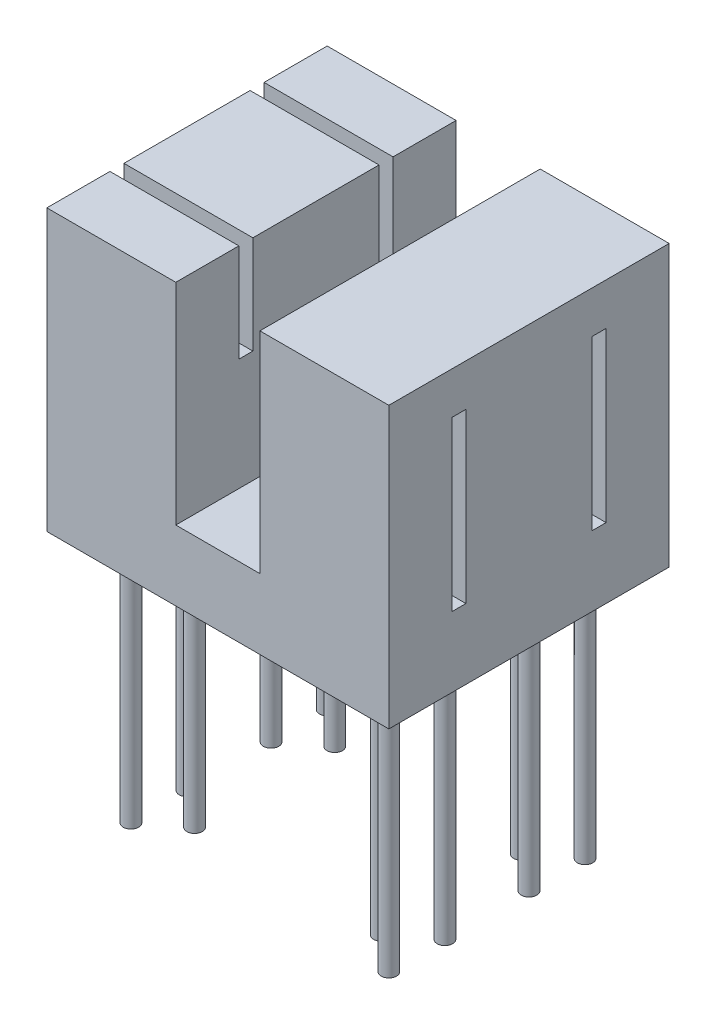
SolidWorks part; units mm, degrees
ref_plane "Front Plane" through (0, 0, 0) normal (0, 0, 1) x (1, 0, 0)
ref_plane "Top Plane" through (0, 0, 0) normal (0, 1, 0) x (1, 0, 0)
ref_plane "Right Plane" through (0, 0, 0) normal (1, 0, 0) x (0, 0, -1)
sketch "Sketch1" plane through (0, 0, 0) normal (0, 1, 0) x (1, 0, 0)
  line L0 (-1.5, 2.5) -> (-1.5, -2.5)
  line L1 (6.1, 2.5) -> (-6.1, 2.5)
  line L2 (6.1, 2.5) -> (6.1, -2.5)
  line L3 (6.1, -2.5) -> (-6.1, -2.5)
  line L4 (-6.1, 2.5) -> (-6.1, -2.5)
  line L5 (6.1, 2.5) -> (-6.1, -2.5) construction
  line L6 (6.1, -2.5) -> (-6.1, 2.5) construction
  line L7 (1.5, 2.5) -> (1.5, -2.5)
  line L8 (0, 4.5301) -> (0, -3.3555) construction
  point P0 (0, 0)
  dimension "D1" = 12.2
  dimension "D2" = 5
  dimension "D3" = 3
extrude "Boss-Extrude1" add sketch "Sketch1" along normal blind 7.5 contours L1 L4 L3 L0 | L1 L7 L3 L2 region at (-3.8, 0, 0) region at (3.8, 0, 0)
extrude "Boss-Extrude2" add sketch "Sketch1<4>" against normal blind 2.5 contours L1 L4 L3 L0 | L7 L1 L0 L3 | L1 L7 L3 L2 region at (0, 0, 0) region at (-3.8, 0, 0) region at (3.8, 0, 0)
sketch "Sketch1<4>" plane through (0, 0, 0) normal (0, 1, 0) x (1, 0, 0) same geometry as "Sketch1"
sketch "Sketch2" plane through (-1.5, 0, 0) normal (1, 0, 0) x (0, 0, -1)
  line L0 (2.5, 7.5) -> (-2.5, 7.5) construction
  line L1 (-0.25, 7.5) -> (0.25, 7.5)
  line L2 (-0.25, 7.5) -> (-0.25, 4)
  line L3 (-0.25, 4) -> (0.25, 4)
  line L4 (0.25, 7.5) -> (0.25, 4)
  line L5 (0, 0) -> (0, 9.2202) construction
  dimension "D1" = 3.5
  dimension "D2" = 0.5
extrude "Cut-Extrude1" cut sketch "Sketch2" against normal through all
sketch "Sketch3" plane through (1.5, 0, 0) normal (-1, 0, 0) x (0, 0, 1)
  line L0 (0, 0) -> (0, 10.1142) construction
  line L1 (-0.25, 0) -> (0.25, 0)
  line L2 (-0.25, 0) -> (-0.25, 6)
  line L3 (-0.25, 6) -> (0.25, 6)
  line L4 (0.25, 0) -> (0.25, 6)
  line L5 (-2.5, 7.5) -> (2.5, 7.5) construction
  line L6 (0, 0) -> (-3.7321, 0) construction
  line L7 (-2.5, 0) -> (2.5, 0) construction
  dimension "D1" = 0.5
  dimension "D2" = 1.5
extrude "Cut-Extrude2" cut sketch "Sketch3" against normal through all
sketch "Sketch5" plane through (0, -2.5, 0) normal (0, -1, 0) x (-1, 0, 0)
  line L0 (-6.1, -2.5) -> (6.1, -2.5) construction
  line L1 (-6.1, 2.5) -> (6.1, 2.5) construction
  line L2 (6.1, 2.5) -> (6.1, -2.5) construction
  line L3 (3.33, 0) -> (5.3719, 0) construction
  circle A0 centre (4.6, -1) radius 0.275
  circle A1 centre (4.6, 1) radius 0.275
  circle A4 centre (3.33, 0) radius 0.275
  dimension "D2" = 1.5
  dimension "D3" = 1.5
  dimension "D4" = 1.5
  dimension "D6" = 1.27
extrude "Boss-Extrude3" add sketch "Sketch5" along normal blind 9
mirror "Mirror2" about plane through (0, 0, 0) normal (1, 0, 0) of "Boss-Extrude3"
mirror "Mirror1" about plane through (0, 7.5, -2.5) normal (0, 0, 1) of "Mirror2", "Boss-Extrude2", "Boss-Extrude1", "Cut-Extrude1", "Cut-Extrude2", "Boss-Extrude3"
